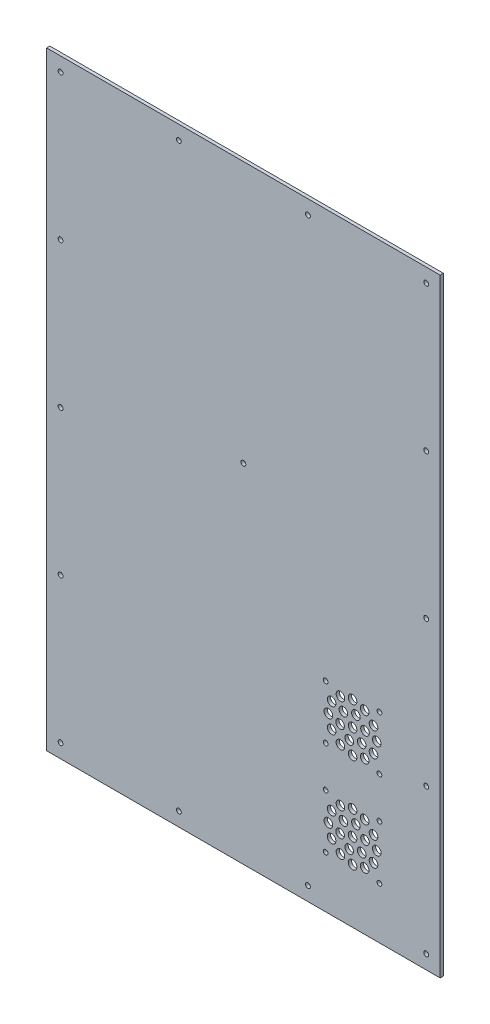
SolidWorks part; units mm, degrees
ref_plane "Спереди" through (0, 0, 0) normal (0, 0, 1) x (1, 0, 0)
ref_plane "Сверху" through (0, 0, 0) normal (0, 1, 0) x (1, 0, 0)
ref_plane "Справа" through (0, 0, 0) normal (1, 0, 0) x (0, 0, -1)
sketch "Эскиз1" plane through (0, 0, 0) normal (0, 0, 1) x (1, 0, 0)
  line L0 (0, 0) -> (366, 0)
  line L1 (0, 0) -> (0, 566)
  line L2 (366, 0) -> (366, 566)
  line L3 (0, 566) -> (366, 566)
  dimension "D1" = 566
  dimension "D2" = 366
extrude "Бобышка-Вытянуть1" add sketch "Эскиз1" along normal blind 3
sketch "Эскиз2" plane through (0, 0, 3) normal (0, 0, 1) x (1, 0, 0)
  line L0 (3, 563) -> (363, 563) construction
  line L1 (3, 563) -> (3, 3) construction
  line L2 (363, 563) -> (363, 3) construction
  line L3 (3, 3) -> (363, 3) construction
  line L4 (0, 566) -> (0, 0) construction
  line L5 (0, 0) -> (366, 0) construction
  dimension "D1" = 560
  dimension "D2" = 360
  dimension "D3" = 3
  dimension "D4" = 3
sketch "Эскиз5" plane through (0, 0, 0) normal (0, 0, -1) x (-1, 0, 0)
  line L0 (-353, 553) -> (-13, 553) construction
  line L1 (-353, 553) -> (-353, 13) construction
  line L2 (-13, 553) -> (-13, 13) construction
  line L3 (-353, 13) -> (-13, 13) construction
  line L4 (-366, 566) -> (0, 566) construction
  line L5 (-366, 0) -> (-366, 566) construction
  line L6 (0, 566) -> (0, 0) construction
  line L7 (0, 0) -> (-366, 0) construction
  line L8 (-366, 23) -> (-343, 23) construction
  line L9 (-366, 23) -> (-366, 0) construction
  line L10 (-343, 23) -> (-343, 0) construction
  line L11 (-366, 0) -> (-343, 0) construction
  line L12 (0, 0) -> (0, 23) construction
  line L13 (0, 0) -> (-23, 0) construction
  line L14 (0, 23) -> (-23, 23) construction
  line L15 (-23, 0) -> (-23, 23) construction
  line L16 (-366, 566) -> (-343, 566) construction
  line L17 (-366, 566) -> (-366, 543) construction
  line L18 (-343, 566) -> (-343, 543) construction
  line L19 (-366, 543) -> (-343, 543) construction
  line L20 (0, 566) -> (0, 543) construction
  line L21 (0, 566) -> (-23, 566) construction
  line L22 (0, 543) -> (-23, 543) construction
  line L23 (-23, 566) -> (-23, 543) construction
  line L24 (-13, 283) -> (-353, 283) construction
  line L25 (-183, 553) -> (-183, 13) construction
  line L26 (0, 0) -> (-366, 0) construction
  circle A0 centre (-353, 553) radius 2.25
  circle A1 centre (-13, 553) radius 2.25
  circle A3 centre (-243, 553) radius 2.25
  circle A4 centre (-123, 553) radius 2.25
  circle A5 centre (-353, 418) radius 2.25
  circle A6 centre (-353, 283) radius 2.25
  circle A7 centre (-353, 148) radius 2.25
  circle A8 centre (-353, 13) radius 2.25
  circle A9 centre (-123, 13) radius 2.25
  circle A10 centre (-243, 13) radius 2.25
  circle A11 centre (-13, 418) radius 2.25
  circle A12 centre (-13, 283) radius 2.25
  circle A13 centre (-13, 148) radius 2.25
  circle A14 centre (-13, 13) radius 2.25
  dimension "D13" = 4.5
  dimension "D14" = 4.5
  dimension "D15" = 110
  dimension "D17" = 4.5
  dimension "D18" = 4.5
  dimension "D19" = 110
  dimension "D22" = 135
  dimension "D23" = 135
  dimension "D24" = 110
  dimension "D25" = 5
  dimension "D26" = 135
  dimension "D27" = 110
  dimension "D28" = 120
  dimension "D29" = 4.5
  dimension "D30" = 4.5
  dimension "D1" = 13
  dimension "D2" = 13
  dimension "D3" = 13
  dimension "D4" = 13
  dimension "D5" = 23
  dimension "D6" = 23
  dimension "D7" = 23
  dimension "D8" = 23
  dimension "D9" = 23
  dimension "D10" = 23
  dimension "D11" = 23
  dimension "D12" = 23
  dimension "D21" = 5
extrude "Вырез-Вытянуть2" cut sketch "Эскиз5" against normal through all
sketch "Sketch1" plane through (0, 0, 3) normal (0, 0, 1) x (1, 0, 0)
  line L1 (343, 333) -> (23, 333) construction
  line L2 (183, 333) -> (183, 323) construction
  circle A0 centre (183, 323) radius 2.25
  dimension "D1" = 4.5
  dimension "D2" = 10
extrude "Cut-Extrude1" cut sketch "Sketch1" against normal through all
sketch "Эскиз6" plane through (0, 0, 0) normal (0, 0, -1) x (-1, 0, 0)
  line L0 (-284.5, 73) -> (-284.5, 45.5) construction
  line L1 (-284.5, 161) -> (-300.4099, 145.0901) construction
  line L2 (-284.5, 73) -> (-284.5, 161) construction
  line L3 (-284.5, 73) -> (-296.5, 73) construction
  line L5 (-284.5, 73) -> (-292.9853, 64.5147) construction
  line L6 (-309.5, 98) -> (-259.5, 98) construction
  line L7 (-309.5, 98) -> (-309.5, 48) construction
  line L8 (-309.5, 48) -> (-259.5, 48) construction
  line L9 (-259.5, 98) -> (-259.5, 48) construction
  line L10 (-309.5, 98) -> (-259.5, 48) construction
  line L11 (-309.5, 48) -> (-259.5, 98) construction
  line L12 (-309.5, 136) -> (-259.5, 136) construction
  line L13 (-309.5, 136) -> (-309.5, 186) construction
  line L14 (-309.5, 186) -> (-259.5, 186) construction
  line L15 (-259.5, 136) -> (-259.5, 186) construction
  line L16 (-309.5, 136) -> (-259.5, 186) construction
  line L17 (-309.5, 186) -> (-259.5, 136) construction
  arc A0 (-292.5, 46.6894) -> (-258.8826, 63) centre (-284.5, 73) ccw construction
  arc A1 (-292.5, 46.6894) -> (-258.8826, 63) centre (-284.5, 73) ccw construction
  circle A2 centre (-284.5, 73) radius 27.5 construction
  circle A3 centre (-284.5, 73) radius 22.5 construction
  circle A4 centre (-284.5, 73) radius 12 construction
  circle A5 centre (-284.5, 50.5) radius 4
  circle A6 centre (-295.75, 53.5144) radius 4
  circle A7 centre (-303.9856, 61.75) radius 4
  circle A8 centre (-307, 73) radius 4
  circle A9 centre (-303.9856, 84.25) radius 4
  circle A10 centre (-295.75, 92.4856) radius 4
  circle A11 centre (-284.5, 95.5) radius 4
  circle A12 centre (-273.25, 92.4856) radius 4
  circle A13 centre (-265.0144, 84.25) radius 4
  circle A14 centre (-262, 73) radius 4
  circle A15 centre (-281.3942, 61.4089) radius 4
  circle A16 centre (-292.9853, 64.5147) radius 4
  circle A17 centre (-296.0911, 76.1058) radius 4
  circle A18 centre (-287.6058, 84.5911) radius 4
  circle A19 centre (-276.0147, 81.4853) radius 4
  circle A20 centre (-284.5, 73) radius 4
  circle A21 centre (-265.0144, 61.75) radius 4
  circle A22 centre (-272.9089, 69.8942) radius 4
  circle A23 centre (-284.5, 161) radius 12 construction
  circle A24 centre (-273.25, 53.5144) radius 4
  circle A25 centre (-284.5, 161) radius 22.5 construction
  circle A26 centre (-284.5, 138.5) radius 4
  circle A27 centre (-295.75, 141.5144) radius 4
  circle A28 centre (-303.9856, 149.75) radius 4
  circle A29 centre (-307, 161) radius 4
  circle A30 centre (-303.9856, 172.25) radius 4
  circle A31 centre (-295.75, 180.4856) radius 4
  circle A32 centre (-284.5, 183.5) radius 4
  circle A33 centre (-273.25, 180.4856) radius 4
  circle A34 centre (-265.0144, 172.25) radius 4
  circle A35 centre (-262, 161) radius 4
  circle A36 centre (-265.0144, 149.75) radius 4
  circle A37 centre (-273.25, 141.5144) radius 4
  circle A38 centre (-292.9853, 152.5147) radius 4
  circle A39 centre (-296.0911, 164.1058) radius 4
  circle A40 centre (-287.6058, 172.5911) radius 4
  circle A41 centre (-276.0147, 169.4853) radius 4
  circle A42 centre (-272.9089, 157.8942) radius 4
  circle A43 centre (-281.3942, 149.4089) radius 4
  circle A44 centre (-284.5, 161) radius 4
  circle A45 centre (-309.5, 98) radius 2.2
  circle A46 centre (-259.5, 98) radius 2.2
  circle A47 centre (-259.5, 48) radius 2.2
  circle A48 centre (-309.5, 48) radius 2.2
  circle A49 centre (-309.5, 186) radius 2.2
  circle A50 centre (-259.5, 186) radius 2.2
  circle A51 centre (-259.5, 136) radius 2.2
  circle A52 centre (-309.5, 136) radius 2.2
  point P30 (-284.5, 73)
  point P40 (-296, 150)
  point P54 (-284.5, 73)
  point P78 (-284.5, 161)
  point P80 (-292.9853, 152.5147)
  point P95 (-284.5, 161)
  dimension "D1" = 8
  dimension "D2" = 45
  dimension "D5" = 6
  dimension "D6" = 45
  dimension "D7" = 24
  dimension "D10" = 8
  dimension "D4" = 8
  dimension "D9" = 45
  dimension "D11" = 8
  dimension "D8" = 24
  dimension "D12" = 12
  dimension "D14" = 8
  dimension "D16" = 8
  dimension "D19" = 4.4
  dimension "D20" = 4.4
  dimension "D13" = 45
  dimension "D17" = 50
  dimension "D18" = 50
  dimension "D21" = 50
  dimension "D22" = 50
  dimension "D3" = 12
  dimension "D15" = 6
extrude "Вырез-Вытянуть3" cut sketch "Эскиз6" against normal through all
